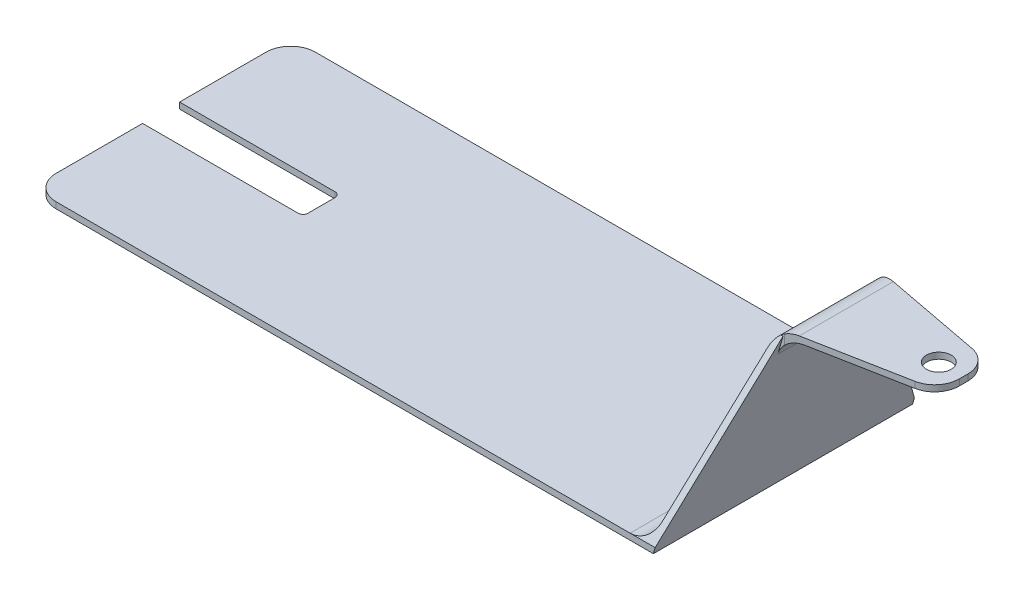
SolidWorks part; units mm, degrees
material "PBT General Purpose"
ref_plane "Front Plane" through (0, 0, 0) normal (0, 0, 1) x (1, 0, 0)
ref_plane "Top Plane" through (0, 0, 0) normal (0, 1, 0) x (1, 0, 0)
ref_plane "Right Plane" through (0, 0, 0) normal (1, 0, 0) x (0, 0, -1)
sketch "Sketch1" plane through (0, 0, 0) normal (0, 0, 1) x (1, 0, 0)
  line L0 (125, 1.25) -> (145, 1.25) construction
  line L1 (-125, -1.25) -> (125, -1.25)
  line L2 (-125, -1.25) -> (-125, 1.25)
  line L3 (-125, 1.25) -> (125, 1.25)
  line L4 (125, -1.25) -> (125, 1.25)
  line L5 (-125, -1.25) -> (125, 1.25) construction
  line L6 (-125, 1.25) -> (125, -1.25) construction
  line L7 (145, 1.25) -> (145, 71.25) construction
  line L8 (125, 1.25) -> (145, 71.25)
  line L9 (146.8858, 68.75) -> (126.8858, -1.25)
  line L10 (125, -1.25) -> (126.8858, -1.25)
  line L11 (145, 71.25) -> (200, 71.25)
  line L12 (200, 71.25) -> (200, 68.75)
  line L13 (200, 68.75) -> (146.8858, 68.75)
  point P0 (0, 0)
  point P10 (0, 0)
  point P14 (170, 56.3319)
  point P15 (170.9954, 56.3319)
  point P16 (171.1418, 56.3304)
  dimension "D1" = 2.5
  dimension "D2" = 250
  dimension "D3" = 20
  dimension "D4" = 70
  dimension "D5" = 2.5
  dimension "D6" = 55
  dimension "D7" = 2.5
extrude "Boss-Extrude1" add sketch "Sketch1" along normal blind 105 contours L1 L10 L9 L13 L12 L11 L8 L3 L2
sketch "Sketch2" plane through (0, 1.25, 0) normal (0, 1, 0) x (1, 0, 0)
  line L0 (-125, -105) -> (-125, 0) construction
  line L1 (-125, -45) -> (-60, -45)
  line L2 (-125, -45) -> (-125, -60)
  line L3 (-125, -60) -> (-60, -60)
  line L4 (-60, -45) -> (-60, -60)
  line L5 (-125, 0) -> (-125, -45) construction
  line L6 (-125, -60) -> (-125, -105) construction
  dimension "D1" = 65
  dimension "D2" = 15
extrude "Cut-Extrude1" cut sketch "Sketch2" against normal up to next
ref_plane "Plane2" through (125, 0, 0) normal (1, 0, 0) x (0, 0, -1)
sketch "Sketch11" plane through (125, 0, 0) normal (1, 0, 0) x (0, 0, -1)
  line L0 (-105, 71.25) -> (0, 71.25) construction
  line L1 (-105, 71.25) -> (0, 71.25) construction
  line L2 (-32.5, 68.75) -> (-72.5, 68.75)
  line L3 (-52.5, 71.25) -> (-52.5, 68.75) construction
  line L4 (-105, 1.25) -> (-72.5, 68.75)
  line L5 (-32.5, 68.75) -> (0, 1.25)
  line L6 (-105, 1.25) -> (-105, 71.25)
  line L7 (-72.5, 68.75) -> (-72.5, 71.25)
  line L8 (-72.5, 71.25) -> (-105, 71.25)
  line L9 (-32.5, 68.75) -> (-32.5, 71.25)
  line L10 (-32.5, 71.25) -> (0, 71.25)
  line L11 (0, 71.25) -> (0, 1.25)
  dimension "D1" = 2.5
  dimension "D2" = 40
extrude "Cut-Extrude12" cut sketch "Sketch11" along normal through all contours L11 L10 L9 L5 | L7 L8 L6 L4 region at (125, 47.8879, 93.7931) region at (125, 47.8879, 11.2069)
sketch "Sketch12" plane through (0, 71.25, 0) normal (0, 1, 0) x (1, 0, 0)
  line L0 (147.5, -72.5) -> (200, -62.5)
  line L1 (200, -72.5) -> (200, -32.5) construction
  line L2 (200, -42.5) -> (200, -62.5)
  line L3 (200, -62.5) -> (200, -72.5)
  line L5 (200, -72.5) -> (147.5, -72.5)
  line L6 (147.5, -32.5) -> (200, -42.5)
  line L7 (200, -32.5) -> (147.5, -32.5)
  line L8 (200, -32.5) -> (200, -42.5)
  line L9 (147.5, -32.5) -> (147.5, -72.5)
  line L10 (200, -32.5) -> (145, -32.5) construction
  line L11 (200, -72.5) -> (145, -72.5) construction
  line L12 (145, -72.5) -> (145, -32.5) construction
  point P13 (0, 0)
  point P22 (0, 0)
  line M8 (200, -32.5) -> (145, -32.5)
  line M10 (145, -72.5) -> (200, -72.5)
  line M11 (200, -72.5) -> (200, -32.5)
  dimension "D1" = 20
  dimension "D2" = 2.5
extrude "Cut-Extrude14" cut sketch "Sketch12" against normal up to next contours L0 M10 M11 | L6 M8 M11 region at (182.5, 71.25, 69.1667) region at (182.5, 71.25, 35.8333)
fillet "Fillet1" radius 10 2 edges at (200, 70, 42.5) (200, 70, 62.5)
fillet "Fillet2" radius 10 2 edges at (145, 71.25, 52.5) (146.8858, 68.75, 52.5)
fillet "Fillet3" radius 10 1 edges at (125, 1.25, 52.5)
fillet "Fillet4" radius 2 2 edges at (-60, 0, 45) (-60, 0, 60)
sketch "Sketch13" plane through (0, 71.25, 0) normal (0, 1, 0) x (1, 0, 0)
  line L0 (200, -52.5) -> (190, -52.5) construction
  line L1 (200, -54.225) -> (200, -50.775) construction
  circle A0 centre (190, -52.5) radius 5
  dimension "D1" = 10
  dimension "D2" = 10
extrude "Cut-Extrude15" cut sketch "Sketch13" against normal up to next contours A0
fillet "Fillet5" radius 10 2 edges at (-125, 0, 0) (-125, 0, 105)
